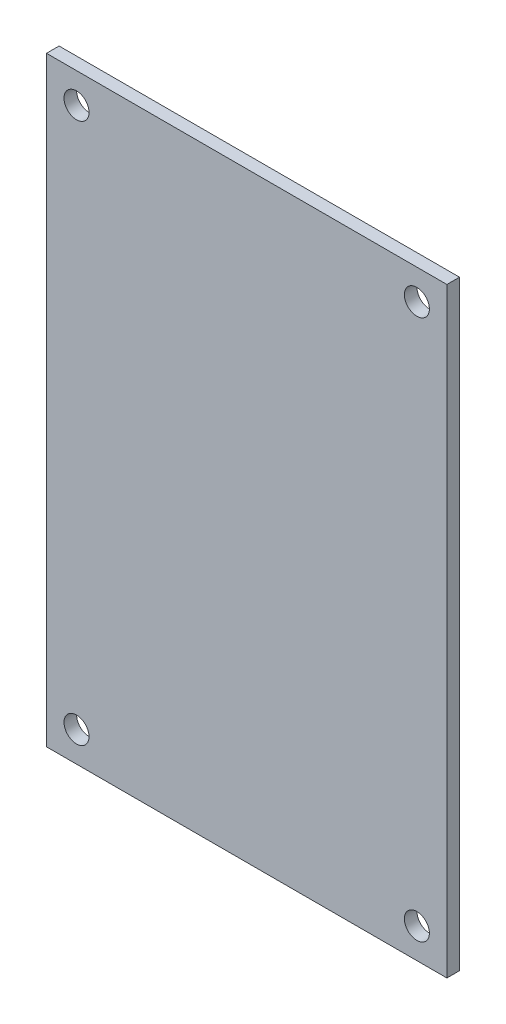
SolidWorks part; units mm, degrees
ref_plane "Front Plane" through (0, 0, 0) normal (0, 0, 1) x (1, 0, 0)
ref_plane "Top Plane" through (0, 0, 0) normal (0, 1, 0) x (1, 0, 0)
ref_plane "Right Plane" through (0, 0, 0) normal (1, 0, 0) x (0, 0, -1)
sketch "Sketch1" plane through (0, 0, 0) normal (0, 0, 1) x (1, 0, 0)
  line L1 (25.4, -38.1) -> (-25.4, -38.1)
  line L2 (25.4, -38.1) -> (25.4, 38.1)
  line L3 (25.4, 38.1) -> (-25.4, 38.1)
  line L4 (-25.4, -38.1) -> (-25.4, 38.1)
  line L5 (25.4, -38.1) -> (-25.4, 38.1) construction
  line L6 (25.4, 38.1) -> (-25.4, -38.1) construction
  point P0 (0, 0)
  dimension "D1" = 50.8
  dimension "D2" = 76.2
extrude "Boss-Extrude1" add sketch "Sketch1" along normal blind 1.6002
sketch "Sketch2" plane through (0, 0, 1.6002) normal (0, 0, 1) x (1, 0, 0)
  line L0 (25.4, 38.1) -> (-25.4, 38.1) construction
  line L1 (-25.4, 38.1) -> (-25.4, -38.1) construction
  line L2 (0, -0.8801) -> (0, 0.8801) construction
  line L3 (0.8801, 0) -> (-0.8801, 0) construction
  line L5 (-21.59, 34.29) -> (21.59, 34.29) construction
  line L6 (-21.59, 34.29) -> (-21.59, -34.29) construction
  line L7 (-21.59, -34.29) -> (21.59, -34.29) construction
  line L8 (21.59, 34.29) -> (21.59, -34.29) construction
  circle A0 centre (-21.59, 34.29) radius 1.5875
  circle A2 centre (21.59, 34.29) radius 1.5875
  circle A3 centre (21.59, -34.29) radius 1.5875
  circle A4 centre (-21.59, -34.29) radius 1.5875
  dimension "D1" = 3.175
  dimension "D2" = 3.81
  dimension "D3" = 3.81
  dimension "D4" = 43.18
  dimension "D5" = 68.58
extrude "Cut-Extrude1" cut sketch "Sketch2" against normal up to next
